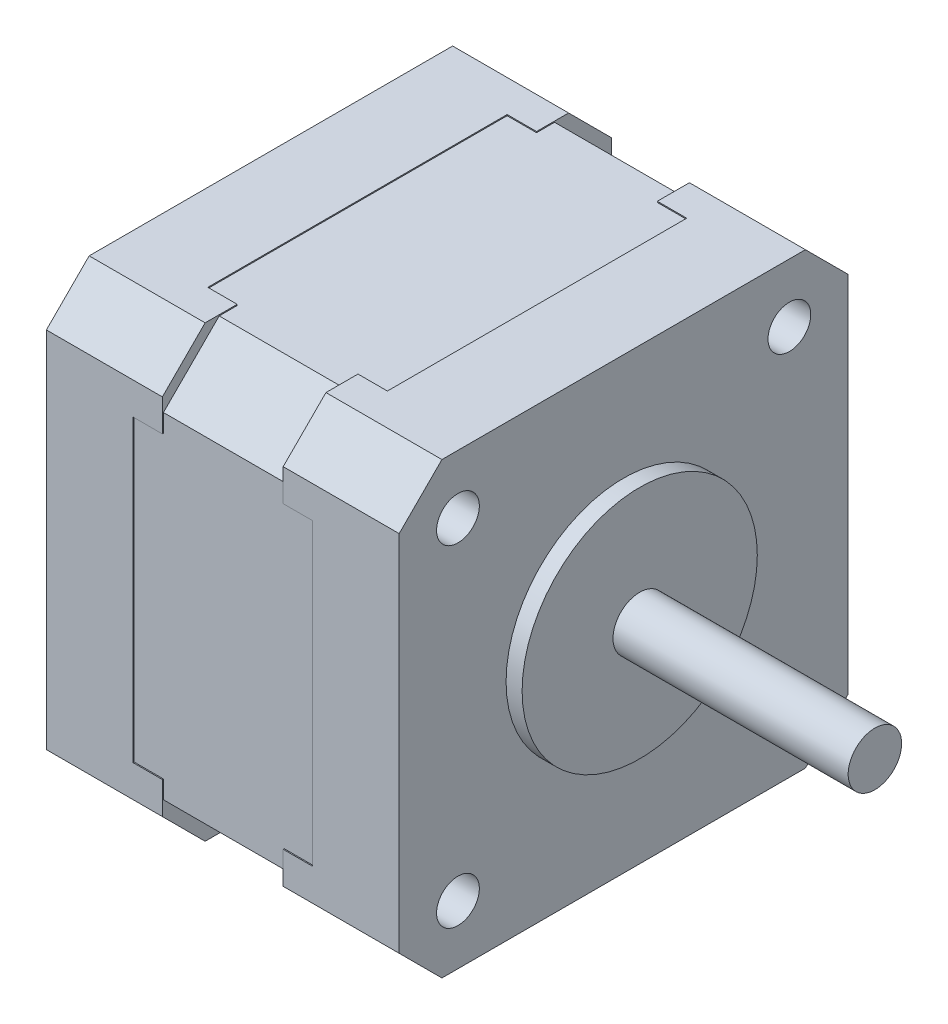
SolidWorks part; units mm, degrees
ref_plane "Alzado" through (0, 0, 0) normal (0, 0, 1) x (1, 0, 0)
ref_plane "Planta" through (0, 0, 0) normal (0, 1, 0) x (1, 0, 0)
ref_plane "Vista lateral" through (0, 0, 0) normal (1, 0, 0) x (0, 0, -1)
ref_plane "Plano1" through (-5.65, 0, 0) normal (-1, 0, 0) x (0, -1, 0)
sketch "Croquis1" plane through (-5.65, 0, 0) normal (-1, 0, 0) x (0, -1, 0)
  line L0 (20.9, -20.9) -> (20.9, 20.9)
  line L1 (20.9, 20.9) -> (-20.9, 20.9)
  line L2 (-20.9, 20.9) -> (-20.9, -20.9)
  line L3 (-20.9, -20.9) -> (20.9, -20.9)
extrude "Saliente-Extruir1" add sketch "Croquis1" against normal blind 11.3
sketch "Croquis2" plane through (5.65, 0, 0) normal (1, 0, 0) x (0, 0, -1)
  line L0 (21, 20.9) -> (21, -21)
  line L1 (21, -21) -> (-21, -21)
  line L2 (-21, -21) -> (-21, 20.9)
  line L3 (-21, 20.9) -> (21, 20.9)
extrude "Saliente-Extruir2" add sketch "Croquis2" along normal blind 10.85
sketch "Croquis3" plane through (0, 20.9, 0) normal (0, 1, 0) x (-1, 0, 0)
  line L0 (-5.65, -21) -> (-16.5, -21)
  line L1 (-16.5, -21) -> (-16.5, 21)
  line L2 (-16.5, 21) -> (-5.65, 21)
  line L3 (-5.65, 21) -> (-5.65, -21)
extrude "Saliente-Extruir3" add sketch "Croquis3" along normal blind 0.1
ref_plane "Plano2" through (-5.65, 0, 0) normal (1, 0, 0) x (0, 0, -1)
sketch "Croquis4" plane through (-5.65, 0, 0) normal (1, 0, 0) x (0, 0, -1)
  line L0 (21, 21) -> (-21, 21)
  line L1 (-21, 21) -> (-21, -21)
  line L2 (-21, -21) -> (21, -21)
  line L3 (21, -21) -> (21, 21)
extrude "Saliente-Extruir4" add sketch "Croquis4" against normal blind 10.85
ref_plane "Plano3" through (8.4, 0, 0) normal (1, 0, 0) x (0, 0, -1)
sketch "Croquis5" plane through (8.4, 0, 0) normal (1, 0, 0) x (0, 0, -1)
  line L0 (20.9, 14) -> (20.9, -14)
  line L1 (20.9, -14) -> (21, -14)
  line L2 (21, -14) -> (21, 14)
  line L3 (21, 14) -> (20.9, 14)
extrude "Cortar-Extruir1" cut sketch "Croquis5" against normal up to next
ref_plane "Plano4" through (-8.4, 0, 0) normal (-1, 0, 0) x (0, -1, 0)
sketch "Croquis6" plane through (-8.4, 0, 0) normal (-1, 0, 0) x (0, -1, 0)
  line L0 (-14, 21) -> (-14, 20.9)
  line L1 (-14, 20.9) -> (14, 20.9)
  line L2 (14, 20.9) -> (14, 21)
  line L3 (14, 21) -> (-14, 21)
extrude "Cortar-Extruir2" cut sketch "Croquis6" against normal up to next
sketch "Croquis7" plane through (0, -21, 0) normal (0, -1, 0) x (1, 0, 0)
  line L0 (8.4, -14) -> (8.4, 14)
  line L1 (8.4, 14) -> (5.65, 14)
  line L2 (5.65, 14) -> (5.65, -14)
  line L3 (5.65, -14) -> (8.4, -14)
extrude "Cortar-Extruir3" cut sketch "Croquis7" against normal blind 0.1
sketch "Croquis8" plane through (0, 0, 21) normal (0, 0, 1) x (1, 0, 0)
  line L0 (8.4, -14) -> (8.4, 14)
  line L1 (8.4, 14) -> (5.65, 14)
  line L2 (5.65, 14) -> (5.65, -14)
  line L3 (5.65, -14) -> (8.4, -14)
extrude "Cortar-Extruir4" cut sketch "Croquis8" against normal blind 0.1
sketch "Croquis9" plane through (5.65, 0, 0) normal (-1, 0, 0) x (0, 0, 1)
  line L0 (-14, 20.9) -> (14, 20.9)
  line L1 (14, 20.9) -> (14, 21)
  line L2 (14, 21) -> (-14, 21)
  line L3 (-14, 21) -> (-14, 20.9)
extrude "Cortar-Extruir5" cut sketch "Croquis9" against normal blind 2.75
sketch "Croquis10" plane through (0, -21, 0) normal (0, -1, 0) x (1, 0, 0)
  line L0 (-5.65, -14) -> (-5.65, 14)
  line L1 (-5.65, 14) -> (-8.4, 14)
  line L2 (-8.4, 14) -> (-8.4, -14)
  line L3 (-8.4, -14) -> (-5.65, -14)
extrude "Cortar-Extruir6" cut sketch "Croquis10" against normal blind 0.1
sketch "Croquis11" plane through (0, 0, -21) normal (0, 0, -1) x (-1, 0, 0)
  line L0 (5.65, 14) -> (5.65, -14)
  line L1 (5.65, -14) -> (8.4, -14)
  line L2 (8.4, -14) -> (8.4, 14)
  line L3 (8.4, 14) -> (5.65, 14)
extrude "Cortar-Extruir7" cut sketch "Croquis11" against normal blind 0.1
sketch "Croquis12" plane through (0, 21, 0) normal (0, 1, 0) x (-1, 0, 0)
  line L0 (5.65, 14) -> (5.65, -14)
  line L1 (5.65, -14) -> (8.4, -14)
  line L2 (8.4, -14) -> (8.4, 14)
  line L3 (8.4, 14) -> (5.65, 14)
extrude "Cortar-Extruir8" cut sketch "Croquis12" against normal blind 0.1
sketch "Croquis15" plane through (0, 0, 0) normal (0, 0, 1) x (1, 0, 0)
  line L0 (15.5, 11) -> (15.5, 0)
  line L1 (15.5, 0) -> (40, 0)
  line L2 (40, 0) -> (40, 2.5)
  line L3 (40, 2.5) -> (18, 2.5)
  line L4 (18, 2.5) -> (18, 11)
  line L5 (18, 11) -> (15.5, 11)
  line L6 (15.5, 0) -> (40, 0) construction
revolve "Revolución1" add sketch "Croquis15" angle 360 about L6 reverse direction yes
chamfer "Chaflán1" distance 5.2142 angle 45 4 edges at (0, -20.9, -20.9) (0, -20.9, 20.9)
chamfer "Chaflán2" distance 4 angle 45 8 edges at (-11.075, 21, -21) (-11.075, -21, 21) (11.075, -21, -21) (11.075, 21, -21) (-11.075, 21, 21) (11.075, 21, 21) (-11.075, -21, -21) (11.075, -21, 21)
ref_plane "Plano5" through (12.45, 0, 0) normal (1, 0, 0) x (0, 0, -1)
sketch "Croquis18" plane through (12.45, 0, 0) normal (1, 0, 0) x (0, 0, -1)
  line L0 (0, 0) -> (0, 2.3727) construction
  line L1 (0, 36.4567) -> (0, 0) construction
  line L2 (0, 0) -> (37.7341, 0) construction
  line L4 (15.5, -15.5) -> (-15.5, -15.5) construction
  line L5 (15.5, -15.5) -> (15.5, 15.5) construction
  line L6 (15.5, 15.5) -> (-15.5, 15.5) construction
  line L7 (-15.5, -15.5) -> (-15.5, 15.5) construction
  line L8 (15.5, -15.5) -> (-15.5, 15.5) construction
  line L9 (15.5, 15.5) -> (-15.5, -15.5) construction
  circle A0 centre (-15.5, 15.5) radius 2
  circle A1 centre (15.5, 15.5) radius 2
  circle A2 centre (15.5, -15.5) radius 2
  circle A3 centre (-15.5, -15.5) radius 2
  dimension "D3" = 4
  dimension "D1" = 15.5
  dimension "D2" = 15.5
extrude "Cortar-Extruir10" cut sketch "Croquis18" against normal blind 3 and the other way blind 6
